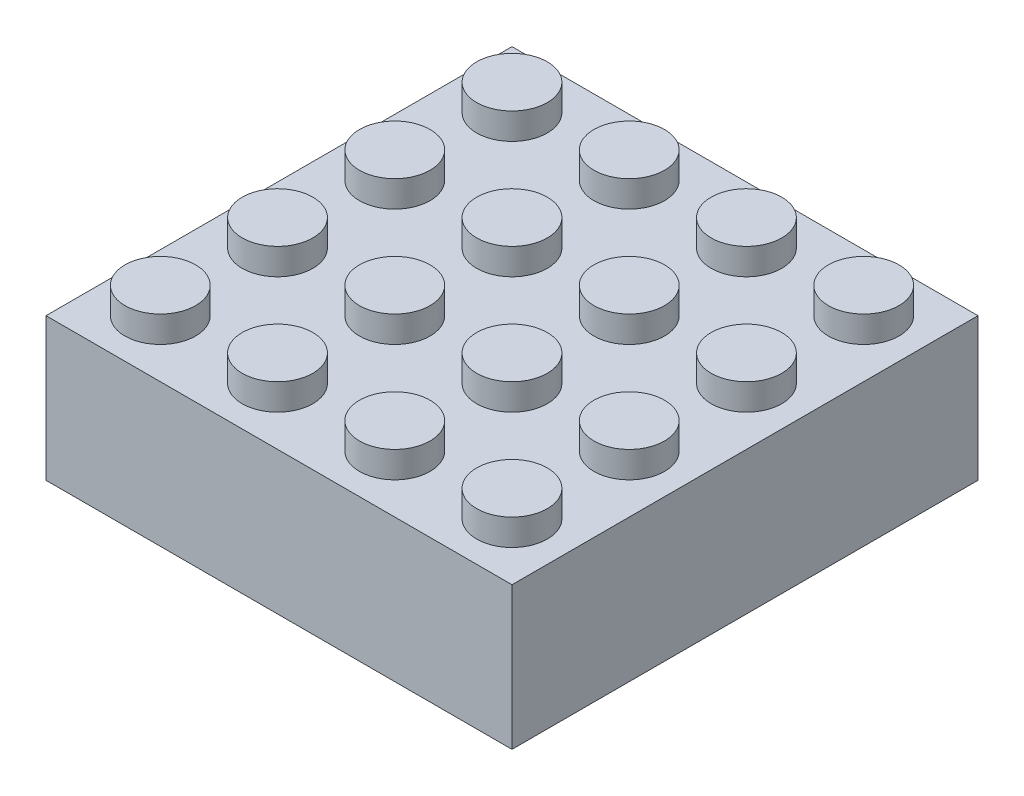
SolidWorks part; units mm, degrees
ref_plane "Front Plane" through (0, 0, 0) normal (0, 0, 1) x (1, 0, 0)
ref_plane "Top Plane" through (0, 0, 0) normal (0, 1, 0) x (1, 0, 0)
ref_plane "Right Plane" through (0, 0, 0) normal (1, 0, 0) x (0, 0, -1)
sketch "Sketch1" plane through (0, 0, 0) normal (0, 1, 0) x (1, 0, 0)
  line L1 (0, 0) -> (31.8, 0)
  line L2 (0, 0) -> (0, 31.8)
  line L3 (0, 31.8) -> (31.8, 31.8)
  line L4 (31.8, 0) -> (31.8, 31.8)
  dimension "D1" = 31.8
  dimension "D2" = 31.8
sketch "Sketch2" plane through (0, 0, 0) normal (0, 1, 0) x (1, 0, 0)
  line L0 (0, 0) -> (0, 31.8) construction
  line L1 (0, 31.8) -> (31.8, 31.8) construction
  circle A0 centre (3.9, 27.9) radius 2.41
  circle A1 centre (11.9, 27.9) radius 2.41
  circle A2 centre (19.9, 27.9) radius 2.41
  circle A3 centre (27.9, 27.9) radius 2.41
  circle A4 centre (11.9, 19.9) radius 2.41
  circle A5 centre (19.9, 19.9) radius 2.41
  circle A6 centre (27.9, 19.9) radius 2.41
  circle A7 centre (11.9, 11.9) radius 2.41
  circle A8 centre (19.9, 11.9) radius 2.41
  circle A9 centre (27.9, 11.9) radius 2.41
  circle A10 centre (11.9, 3.9) radius 2.41
  circle A11 centre (19.9, 3.9) radius 2.41
  circle A12 centre (27.9, 3.9) radius 2.41
  circle A13 centre (3.9, 19.9) radius 2.41
  circle A14 centre (3.9, 11.9) radius 2.41
  circle A15 centre (3.9, 3.9) radius 2.41
  dimension "D3" = 4.82
  dimension "D1" = 3.9
  dimension "D2" = 3.9
  dimension "D4" = 4
  dimension "D5" = 4
extrude "Boss-Extrude1" add sketch "Sketch2" along normal blind 1.8
extrude "Boss-Extrude2" add sketch "Sketch1" against normal blind 9.73
sketch "Sketch4" plane through (0, -9.73, 0) normal (0, -1, 0) x (1, 0, 0)
  line L1 (26.0857, -15.8744) -> (21.0164, -7.0925)
  line L2 (21.0164, -7.0925) -> (10.8054, -7.0798)
  line L3 (10.8054, -7.0798) -> (5.7143, -15.9291)
  line L4 (5.7143, -15.9291) -> (10.8306, -24.7346)
  line L5 (10.8306, -24.7346) -> (21.0154, -24.7081)
  line L6 (21.0154, -24.7081) -> (26.0857, -15.8744)
  circle A0 centre (15.9, -15.9) radius 10.1858
  point P9 (0, 0)
  point P10 (0, 0)
  point P11 (0, 0)
  point P12 (0, 0)
  point P13 (0, 0)
  point P40 (15.9, -15.9)
  dimension "D1" = 20.3715
extrude "Cut-Extrude1" cut sketch "Sketch4" against normal blind 6.63 contours L6 L1 L2 L3 L4 L5 region at (15.9038, -9.73, -15.9011)
sketch "Sketch9" plane through (0, -9.73, 0) normal (0, -1, 0) x (1, 0, 0)
  line L0 (21.0164, -7.0925) -> (10.8054, -7.0798) construction
  line L2 (11.8054, -7.0811) -> (20.0165, -7.0811)
  line L3 (11.8054, -7.0811) -> (11.8054, -5.5811)
  line L4 (11.8054, -5.5811) -> (20.0165, -5.5811)
  line L5 (20.0165, -7.0811) -> (20.0165, -5.5811)
  dimension "D1" = 1
  dimension "D2" = 1
  dimension "D3" = 1.5
extrude "Boss-Extrude4" add sketch "Sketch9" along normal blind 1.5
sketch "Sketch10" plane through (20.0165, 0, 0) normal (1, 0, 0) x (0, 0, -1)
  line L2 (7.0811, -11.23) -> (7.6811, -10.23)
  line L4 (7.6811, -10.23) -> (7.0811, -9.73)
  line L5 (7.0811, -11.23) -> (7.0811, -9.73)
  point P6 (0, 0)
  point P10 (7.0811, -10.2263)
  dimension "D3" = 1
  dimension "D4" = 0.6
extrude "Boss-Extrude5" add sketch "Sketch10" against normal up to surface (8.211 mm away) up to face at (11.8054, -10.48, -6.3311)
sketch "Sketch11" plane through (20.0165, 0, 0) normal (1, 0, 0) x (0, 0, -1)
  line L0 (6.5811, -11.23) -> (5.5811, -9.73)
  line L1 (7.0811, -11.23) -> (5.5811, -11.23) construction
  line L2 (5.5811, -9.73) -> (5.5811, -11.23)
  line L3 (5.5811, -11.23) -> (6.5811, -11.23)
  dimension "D1" = 1
extrude "Cut-Extrude4" cut sketch "Sketch11" against normal up to next (8.211 mm away)
ref_axis "Axis2" through (15.9, 33.0797, -15.9) along (0, -1, 0)
pattern_circular "CirPattern3" count 6 over 360 about axis through (15.9, 33.0797, -15.9) along (0, -1, 0) of "Boss-Extrude4", "Boss-Extrude5", "Cut-Extrude4"
